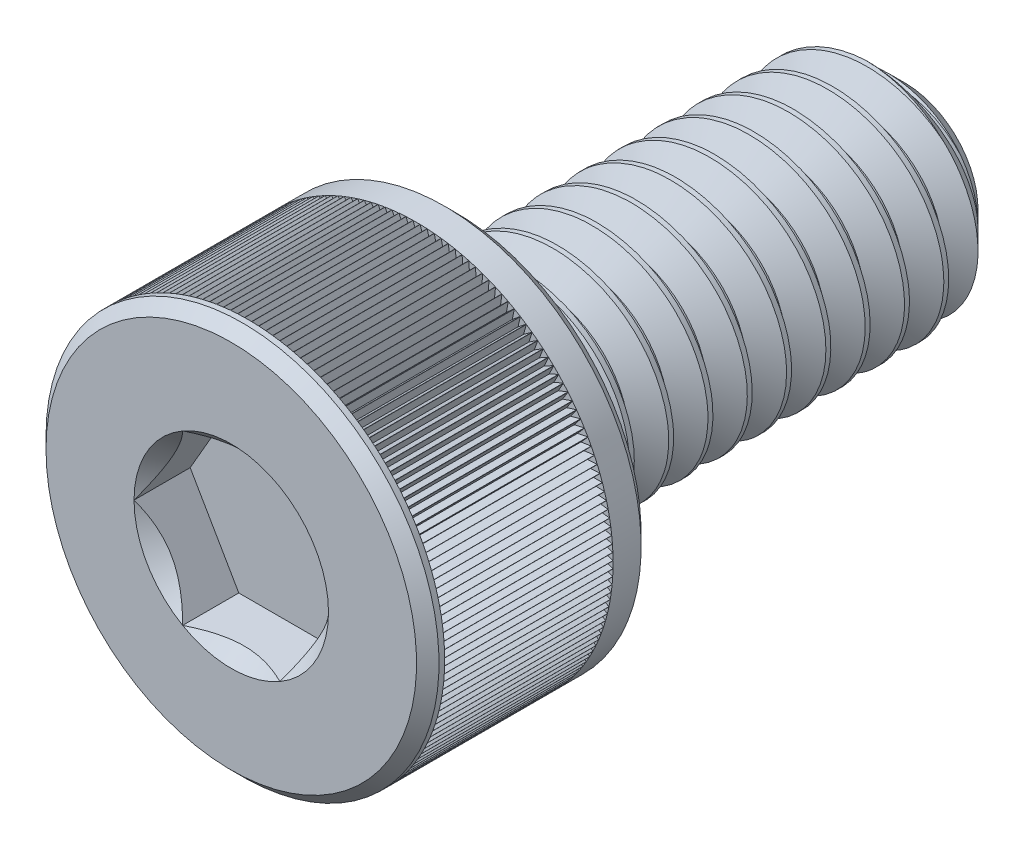
SolidWorks part; units mm, degrees
ref_plane "Front Plane" through (0, 0, 0) normal (0, 0, 1) x (1, 0, 0)
ref_plane "Top Plane" through (0, 0, 0) normal (0, 1, 0) x (1, 0, 0)
ref_plane "Right Plane" through (0, 0, 0) normal (1, 0, 0) x (0, 0, -1)
sketch "Sketch1" plane through (0, 0, 0) normal (1, 0, 0) x (0, 0, -1)
  line L0 (-6, 0) -> (6, 0) construction
  line L1 (6, 0) -> (6, 1.3) construction
  line L2 (6, 1.3) -> (5.3, 2) construction
  line L3 (5.3, 2) -> (-12, 2) construction
  line L5 (-2, 2.25) -> (-2, 3.5) construction
  line L6 (-2, 3.5) -> (-6, 3.5) construction
  line L7 (-6, 3.5) -> (-6, 0) construction
  line L8 (6, 1.3) -> (6, 2) construction
  line L9 (5.9562, 2.0758) -> (6.3062, 1.4696) construction
  line L10 (6.3062, 1.4696) -> (6.6562, 2.0758) construction
  line L11 (6.6562, 2.0758) -> (5.9562, 2.0758) construction
  line L12 (6.3062, 2.0758) -> (6.3062, 2) construction
  line L13 (6.3062, 1.4696) -> (6.3062, 1.5453) construction
  line L14 (6.2625, 1.5453) -> (6.35, 1.5453) construction
  line L15 (6, 2) -> (6.6125, 2) construction
  line L16 (5.9781, 2.0379) -> (6.6344, 2.0379) construction
  line L17 (6, 0) -> (6, -2) construction
  line L18 (-2.2, 3.5) -> (-2, 3.3) construction
  line L19 (-5.8, 3.5) -> (-6, 3.3) construction
  point P0 (-6, 1.5)
  point P3 (3.55, 2)
  point P4 (0, 0)
  point P22 (6.3062, 1.5453)
  point P24 (-12, 2)
  point P25 (6.3062, 2)
  point P28 (6.3062, 2.0379)
  point P29 (3.55, -2)
  point P31 (-4, 3.5)
  point P37 (-2.7, 3.5)
  point P38 (-5.7, 3.5)
  dimension "head height" = 4
  dimension "D1" = 45
  dimension "head dia" = 7
  dimension "thread dia" = 4
  dimension "drive size" = 3
  dimension "pitch" = 0.7
  dimension "D2" = 0.0875
  dimension "D3" = 0.7
  dimension "D4" = 2.45
  dimension "D7" = 0.2
  dimension "D8" = 0.2
  dimension "D9" = 0.2
  dimension "D10" = 0.1
  dimension "D11" = 0.5
  dimension "D12" = 18
  dimension "length" = 8
sketch "Sketch2" plane through (0, 0, 0) normal (1, 0, 0) x (0, 0, -1)
  line L1 (-5.8, 3.5) -> (-2.2, 3.5)
  line L4 (5.3, 2) -> (6, 1.3)
  line L5 (6, 1.3) -> (6, 0)
  line L6 (-2.2, 3.5) -> (-2, 3.3) construction
  line L7 (6, 0) -> (-6, 0)
  line L8 (-5.8, 3.5) -> (-6, 3.3) construction
  line L9 (-2.2, 3.5) -> (-2, 3.3)
  line L10 (-5.8, 3.5) -> (-6, 3.3)
  line L11 (-6, 3.3) -> (-6, 0)
  line L12 (-2, 3.3) -> (-2, 2)
  line L13 (-2, 2) -> (5.3, 2)
revolve "Revolve1" add sketch "Sketch2" angle 360 about L7
sketch "Sketch3" plane through (0, 0, 6) normal (0, 0, 1) x (1, 0, 0)
  line L1 (0.866, 1.5) -> (-0.866, 1.5)
  line L2 (-0.866, 1.5) -> (-1.7321, 0)
  line L3 (-1.7321, 0) -> (-0.866, -1.5)
  line L4 (-0.866, -1.5) -> (0.866, -1.5)
  line L5 (0.866, -1.5) -> (1.7321, 0)
  line L6 (1.7321, 0) -> (0.866, 1.5)
  circle A0 centre (0, 0) radius 1.5 construction
extrude "Cut-Extrude1" cut sketch "Sketch3" against normal offset from surface (1 mm away) 1 up to face at (-3.3, 0, 6)
sketch "Sketch4" plane through (0, 0, 6) normal (0, 0, 1) x (1, 0, 0)
  circle A0 centre (0, 0) radius 1.7321
extrude "Cut-Extrude2" cut sketch "Sketch4" against normal blind 0.5 draft 45
ref_plane "Plane1" through (0, 0, 12) normal (0, 0, 1) x (1, 0, 0)
split "Split1" bodies to split 106 resulting bodies 108 115 split by face at (-3.3, 0, 2)
sketch "Sketch6" plane through (0, 0, -6) normal (0, 0, -1) x (-1, 0, 0)
  circle A0 centre (0, 0) radius 2
curve "Helix/Spiral1" pitch 0.7 height 8.7 radius 2 centre (0, 0, -6) axis (0, 0, 1) start towards (0, 1, 0)
sketch "Sketch7" plane through (0, 0, 0) normal (1, 0, 0) x (0, 0, -1)
  line L0 (5.9781, 2.0379) -> (6.6344, 2.0379)
  line L1 (6.6344, 2.0379) -> (6.35, 1.5453)
  line L2 (6.35, 1.5453) -> (6.2625, 1.5453)
  line L3 (6.2625, 1.5453) -> (5.9781, 2.0379)
sweep "Cut-Sweep1" cut profiles "Sketch7" path "Helix/Spiral1" align with end faces yes
sketch "Sketch8" plane through (0, 0, 2) normal (0, 0, -1) x (-1, 0, 0)
  circle A0 centre (0, 0) radius 2
extrude "Boss-Extrude1" add sketch "Sketch8" along normal through all draft 45
ref_plane "Plane2" through (0, 0, 4) normal (0, 0, 1) x (1, 0, 0)
sketch "Sketch9" plane through (0, 0, 4) normal (0, 0, 1) x (1, 0, 0)
  line L0 (0, 3.325) -> (0.0611, 3.4995)
  line L1 (0, 3.325) -> (-0.0611, 3.4995)
  line L2 (0, 3.5) -> (0, 0) construction
  line L3 (-0.0611, 3.4995) -> (0, 0) construction
  line L4 (0, 0) -> (0.0611, 3.4995) construction
  arc A0 (0.0611, 3.4995) -> (-0.0611, 3.4995) centre (0, 0) ccw
  circle A1 centre (0, 0) radius 3.325 construction
  dimension "D2" = 6.65
  dimension "D3" = 2
extrude "Cut-Extrude4" cut sketch "Sketch9" against normal up to vertex (1.3 mm away) and the other way up to vertex (1.7 mm away) up to point (0, 3.5, 2.7) other way up to point (0, 3.5, 5.7)
pattern_circular "CirPattern2" count 175 over 360 about axis through (0, 0, 6) along (0, 0, -1) of "Cut-Extrude4"
equation "\"D2@Sketch1\"=\"pitch@Sketch1\"/8"
equation "\"D3@Sketch1\"=\"pitch@Sketch1\""
equation "\"D3@Helix/Spiral1\"=\"length@Sketch1\"+\"pitch@Sketch1\""
equation "\"D4@Helix/Spiral1\"=\"pitch@Sketch1\""
equation "\"D4@Sketch1\"=\"pitch@Sketch1\"*3.5"
equation "\"D7@Sketch1\"=\"head height@Sketch1\"*.05"
equation "\"D8@Sketch1\"=\"D7@Sketch1\""
equation "\"D9@Sketch1\"=\"D7@Sketch1\""
equation "\"D10@Sketch1\"=\"D7@Sketch1\"/2"
equation "\"D11@Sketch1\"=\"D10@Sketch1\"*5"
equation "\"D2@Sketch9\"=\"D1@Sketch9\"*.95"
equation "\"D1@CirPattern2\"= ( 360 / \"D3@Sketch9\" ) - 5"
